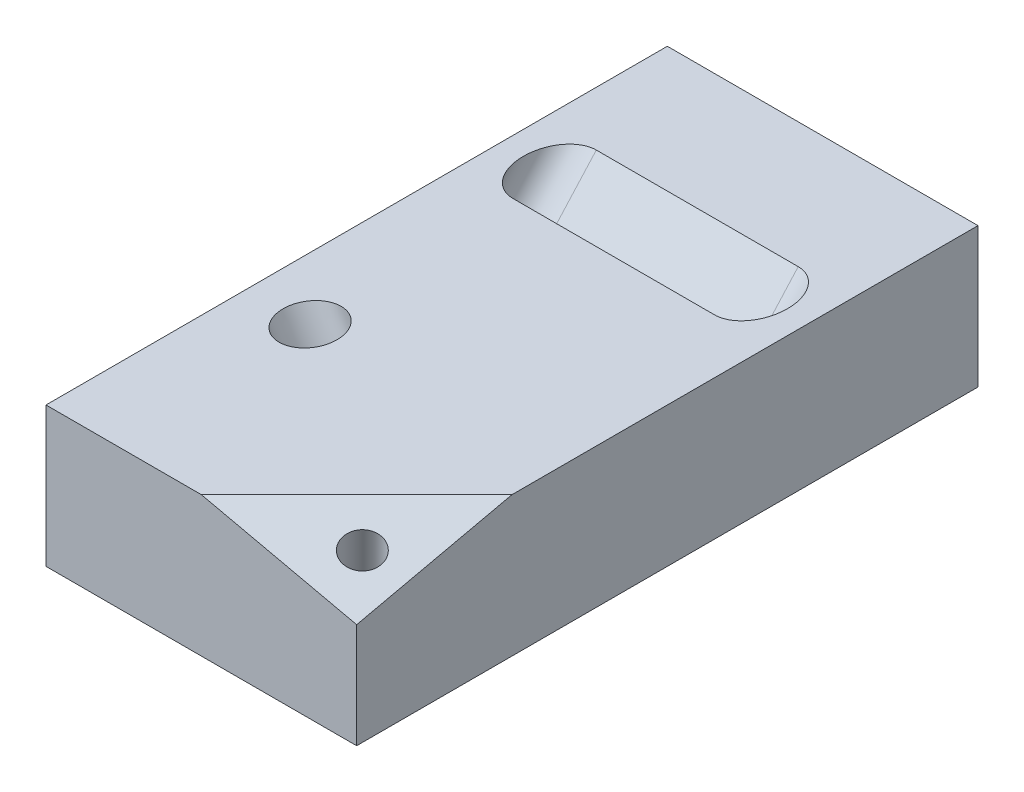
SolidWorks part; units mm, degrees
material "Brass"
ref_plane "Front Plane" through (0, 0, 0) normal (0, 0, 1) x (1, 0, 0)
ref_plane "Top Plane" through (0, 0, 0) normal (0, 1, 0) x (1, 0, 0)
ref_plane "Right Plane" through (0, 0, 0) normal (1, 0, 0) x (0, 0, -1)
sketch "Sketch1" plane through (0, 0, 0) normal (0, 1, 0) x (1, 0, 0)
  line L1 (-100, -200) -> (100, -200)
  line L2 (-100, -200) -> (-100, 200)
  line L3 (-100, 200) -> (100, 200)
  line L4 (100, -200) -> (100, 200)
  line L5 (-100, -200) -> (100, 200) construction
  line L6 (-100, 200) -> (100, -200) construction
  point P0 (0, 0)
  dimension "D1" = 200
  dimension "D2" = 400
extrude "Boss-Extrude1" add sketch "Sketch1" along normal blind 90
sketch "Sketch2" plane through (0, 0, 200) normal (0, 0, 1) x (1, 0, 0)
  line L0 (0, 90) -> (100, 67.5) construction
  line L1 (-100, 90) -> (100, 90) construction
  line L2 (100, 90) -> (100, 0) construction
  dimension "D1" = 100
  dimension "D2" = 22.5
sketch "Sketch3" plane through (100, 0, 0) normal (1, 0, 0) x (0, 0, -1)
  line L0 (-200, 67.5) -> (-100, 90) construction
  line L1 (-200, 90) -> (-200, 0) construction
  line L2 (-200, 90) -> (-200, 67.5) construction
  line L3 (-200, 90) -> (200, 90) construction
  dimension "D1" = 100
ref_plane "Plane1" through (27.5823, 122.588, 27.5823) normal (-0.2144, -0.9529, -0.2144) x (-0.9767, 0.2092, 0.0471)
sketch "Sketch4" plane through (27.5823, 122.588, 27.5823) normal (-0.2144, -0.9529, -0.2144) x (-0.9767, 0.2092, 0.0471)
  line L0 (28.239, -175.3659) -> (-74.1419, -77.8049)
  line L1 (-74.1419, -77.8049) -> (-74.1419, -180.3049)
  line L2 (-74.1419, -180.3049) -> (28.239, -175.3659)
  circle A0 centre (-46.761, -147.8049) radius 11.8135
  dimension "D1" = 75
  dimension "D2" = 70
extrude "Cut-Extrude2" cut sketch "Sketch4" against normal through all contours L0 L1 L2
extrude "Cut-Extrude4" cut sketch "Sketch4<3>" along normal through all contours A0
sketch "Sketch4<3>" plane through (27.5823, 122.588, 27.5823) normal (-0.2144, -0.9529, -0.2144) x (-0.9767, 0.2092, 0.0471) same geometry as "Sketch4"
sketch "Sketch9" plane through (0, 90, 0) normal (0, 1, 0) x (1, 0, 0)
  line L0 (-100, -200) -> (0, -200) construction
  line L1 (-100, 200) -> (-100, -200) construction
  point P0 (-60, -70)
  dimension "D1" = 130
  dimension "D2" = 40
ref_plane "Plane2" through (-63.9711, 110.8013, 0) normal (-0.5, 0.866, 0) x (0, 0, 1)
sketch "Sketch10" plane through (-63.9711, 110.8013, 0) normal (-0.5, 0.866, 0) x (0, 0, 1)
  ellipse E0 centre (70, -6.9615) end of major axis (50, -6.9615) minor radius 15
  point P1 (0, 0)
  dimension "D1" = 30
  dimension "D2" = 20
extrude "Cut-Extrude5" cut sketch "Sketch10" against normal blind 100 contours E0
ref_plane "Plane3" through (0, 149.156, -134.3006) normal (0, 0.7431, -0.6691) x (-1, 0, 0)
sketch "Sketch11" plane through (0, 149.156, -134.3006) normal (0, 0.7431, -0.6691) x (-1, 0, 0)
  line L0 (-65, -8.4072) -> (65, -8.4072) construction
  line L1 (-65, 11.5928) -> (65, 11.5928)
  line L2 (-65, -28.4072) -> (65, -28.4072)
  line L3 (100, -88.4072) -> (100, 208.8507) construction
  line L4 (-100, 134.5362) -> (-100, -88.4072) construction
  line L5 (-100, -88.4072) -> (100, -88.4072) construction
  arc A0 (-65, 11.5928) -> (-65, -28.4072) centre (-65, -8.4072) ccw
  arc A1 (65, -28.4072) -> (65, 11.5928) centre (65, -8.4072) ccw
  point P2 (0, -8.4072)
  dimension "D3" = 20
  dimension "D1" = 35
  dimension "D2" = 35
  dimension "D4" = 60
extrude "Cut-Extrude6" cut sketch "Sketch11" against normal through all contours L1 A1 L2 A0
